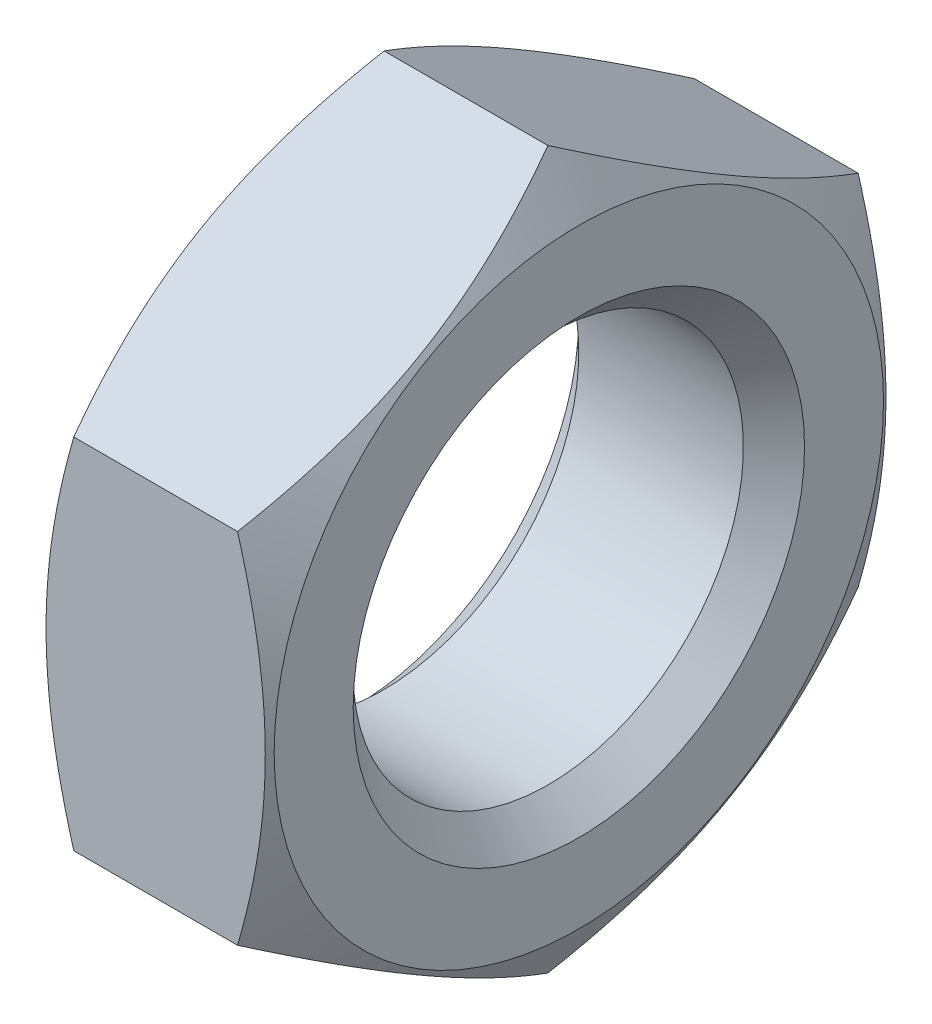
SolidWorks part; units mm, degrees
ref_plane "前视基准面" through (0, 0, 0) normal (0, 0, 1) x (1, 0, 0)
ref_plane "上视基准面" through (0, 0, 0) normal (0, 1, 0) x (1, 0, 0)
ref_plane "右视基准面" through (0, 0, 0) normal (1, 0, 0) x (0, 0, -1)
ref_plane "基准面1" through (0, 0, 0) normal (1, 0, 0) x (0, 0, -1)
sketch "草图1" plane through (0, 0, 0) normal (1, 0, 0) x (0, 0, -1)
  line L0 (-5.5, -3.1754) -> (0, -6.3509)
  line L1 (0, -6.3509) -> (5.5, -3.1754)
  line L2 (5.5, -3.1754) -> (5.5, 3.1754)
  line L3 (5.5, 3.1754) -> (0, 6.3509)
  line L4 (0, 6.3509) -> (-5.5, 3.1754)
  line L5 (-5.5, 3.1754) -> (-5.5, -3.1754)
extrude "凸台-拉伸1" add sketch "草图1" against normal blind 2 and the other way blind 2
ref_plane "基准面2" through (0, 0, 0) normal (0, 0, 1) x (1, 0, 0)
sketch "草图2" plane through (0, 0, 0) normal (0, 0, 1) x (1, 0, 0)
  line L0 (-2, 0) -> (-2, 4)
  line L1 (-2, 4) -> (-1.4585, 3.4585)
  line L2 (-1.4585, 3.4585) -> (1.4585, 3.4585)
  line L3 (1.4585, 3.4585) -> (2, 4)
  line L4 (2, 4) -> (2, 0)
  line L5 (2, 0) -> (-2, 0)
  line L6 (2, 0) -> (-2, 0) construction
revolve "切除-旋转1" cut sketch "草图2" angle 360 about L6 reverse direction yes
cosmetic thread "装饰螺纹线1" parameters "D1"=4, "D2"=8
ref_plane "基准面3" through (0, 0, 0) normal (0, 0, 1) x (1, 0, 0)
sketch "草图3" plane through (0, 0, 0) normal (0, 0, 1) x (1, 0, 0)
  line L0 (-7, 1) -> (-2, 1)
  line L1 (-2, 1) -> (-2, 5.4)
  line L2 (-2, 5.4) -> (0, 8.8641)
  line L3 (0, 8.8641) -> (2, 5.4)
  line L4 (2, 5.4) -> (2, 1)
  line L5 (2, 1) -> (7, 1)
  line L6 (7, 1) -> (7, 13.4)
  line L7 (7, 13.4) -> (-7, 13.4)
  line L8 (-7, 13.4) -> (-7, 1)
  line L9 (50, 0) -> (-50, 0) construction
revolve "切除-旋转2" cut sketch "草图3" angle 360 about L9 reverse direction yes
